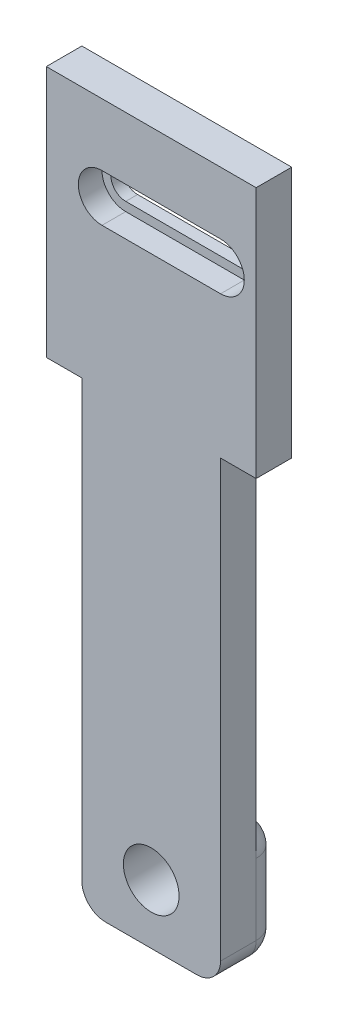
SolidWorks part; units mm, degrees
ref_plane "Front Plane" through (0, 0, 0) normal (0, 0, 1) x (1, 0, 0)
ref_plane "Top Plane" through (0, 0, 0) normal (0, 1, 0) x (1, 0, 0)
ref_plane "Right Plane" through (0, 0, 0) normal (1, 0, 0) x (0, 0, -1)
sketch "Sketch1" plane through (0, 0, 0) normal (0, 0, 1) x (1, 0, 0)
  line L1 (-43.4143, 34.026) -> (-25.7143, 34.026)
  line L2 (-43.4143, 34.026) -> (-43.4143, -25.974)
  line L3 (-43.4143, -25.974) -> (-25.7143, -25.974)
  line L4 (-25.7143, 34.026) -> (-25.7143, -25.974)
  dimension "D1" = 17.7
  dimension "D2" = 60
extrude "Boss-Extrude1" add sketch "Sketch1" along normal blind 3
sketch "Sketch2" plane through (0, 0, 3) normal (0, 0, 1) x (1, 0, 0)
  line L1 (-43.4143, -25.974) -> (-40.4143, -25.974)
  line L2 (-43.4143, -25.974) -> (-43.4143, 12.776)
  line L3 (-43.4143, 12.776) -> (-40.4143, 12.776)
  line L4 (-40.4143, -25.974) -> (-40.4143, 12.776)
  line L5 (-25.7143, -25.974) -> (-28.7143, -25.974)
  line L6 (-25.7143, -25.974) -> (-25.7143, 12.776)
  line L7 (-25.7143, 12.776) -> (-28.7143, 12.776)
  line L8 (-28.7143, -25.974) -> (-28.7143, 12.776)
  dimension "D1" = 38.75
  dimension "D2" = 38.75
  dimension "D3" = 3
  dimension "D4" = 3
extrude "Cut-Extrude1" cut sketch "Sketch2" against normal through all
sketch "Sketch3" plane through (0, 0, 3) normal (0, 0, 1) x (1, 0, 0)
  line L0 (-28.7143, 26.776) -> (-38.7143, 26.776) construction
  line L1 (-28.7143, 25.526) -> (-38.7143, 25.526)
  line L2 (-28.7143, 28.026) -> (-38.7143, 28.026)
  line L3 (-25.7143, 34.026) -> (-43.4143, 34.026) construction
  line L4 (-25.7143, 12.776) -> (-25.7143, 34.026) construction
  arc A0 (-28.7143, 25.526) -> (-28.7143, 28.026) centre (-28.7143, 26.776) ccw
  arc A1 (-38.7143, 28.026) -> (-38.7143, 25.526) centre (-38.7143, 26.776) ccw
  point P2 (-33.7143, 26.776)
  dimension "D3" = 3
  dimension "D1" = 6
  dimension "D2" = 2.5
  dimension "D4" = 10
extrude "Cut-Extrude2" cut sketch "Sketch3" against normal through all
sketch "Sketch4" plane through (0, 0, 3) normal (0, 0, 1) x (1, 0, 0)
  line L0 (-38.7143, 26.776) -> (-28.7143, 26.776) construction
  line L1 (-38.7143, 28.776) -> (-28.7143, 28.776)
  line L2 (-38.7143, 24.776) -> (-28.7143, 24.776)
  arc A0 (-38.7143, 28.776) -> (-38.7143, 24.776) centre (-38.7143, 26.776) ccw
  arc A1 (-28.7143, 24.776) -> (-28.7143, 28.776) centre (-28.7143, 26.776) ccw
  point P4 (-33.7143, 26.776)
  dimension "D1" = 4
extrude "Cut-Extrude3" cut sketch "Sketch4" against normal blind 2
sketch "Sketch5" plane through (0, 0, 0) normal (0, 0, -1) x (-1, 0, 0)
  line L0 (40.4143, -25.974) -> (40.4143, 12.776) construction
  line L1 (28.7143, -25.974) -> (40.4143, -25.974)
  line L2 (28.7143, -25.974) -> (28.7143, -15.974)
  line L3 (28.7143, -15.974) -> (40.4143, -15.974)
  line L4 (40.4143, -25.974) -> (40.4143, -15.974)
  dimension "D1" = 10
extrude "Boss-Extrude2" add sketch "Sketch5" along normal blind 2
sketch "Sketch6" plane through (0, 0, -2) normal (0, 0, -1) x (-1, 0, 0)
  line L0 (28.7143, -25.974) -> (40.4143, -25.974) construction
  circle A0 centre (34.5643, -20.974) radius 2.35
  dimension "D1" = 4.7
  dimension "D2" = 5
extrude "Cut-Extrude4" cut sketch "Sketch6" against normal through all both and the other way through all
fillet "Fillet1" radius 2 1 edges at (-34.5643, -25.974, -2)
fillet "Fillet2" radius 2 1 edges at (-34.5643, -15.974, -2)
fillet "Fillet3" radius 2 4 edges at (-28.7143, -16.5598, -1.4142) (-28.7143, -20.974, -2) (-28.7143, -25.3882, -1.4142) (-28.7143, -25.974, 1.5)
fillet "Fillet4" radius 2 4 edges at (-40.4143, -16.5598, -1.4142) (-40.4143, -20.974, -2) (-40.4143, -25.3882, -1.4142) (-40.4143, -25.974, 1.5)
